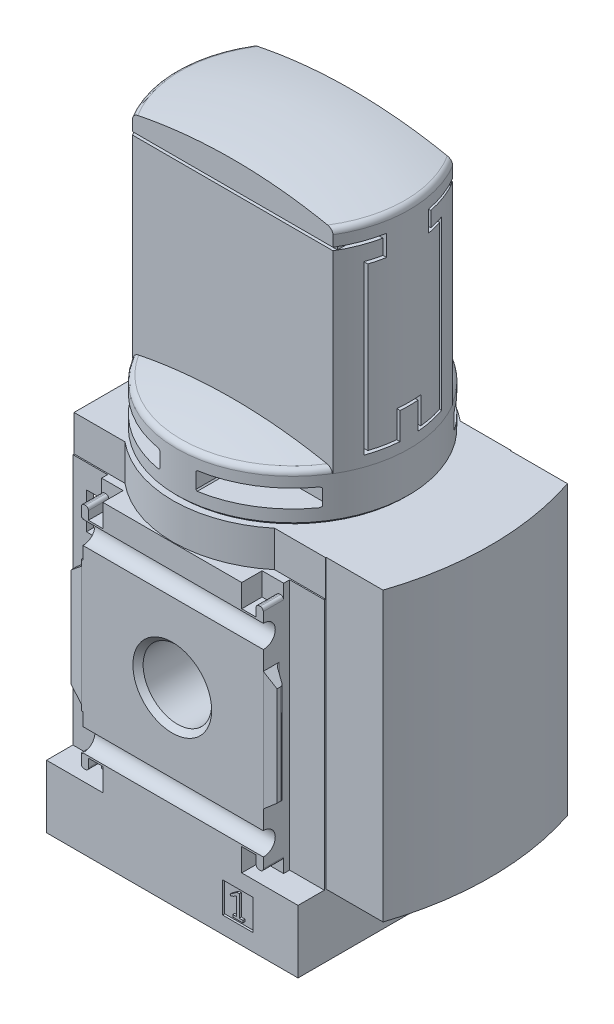
SolidWorks part; units mm, degrees
ref_plane "Front Plane" through (0, 0, 0) normal (0, 0, 1) x (1, 0, 0)
ref_plane "Top Plane" through (0, 0, 0) normal (0, 1, 0) x (1, 0, 0)
ref_plane "Right Plane" through (0, 0, 0) normal (1, 0, 0) x (0, 0, -1)
ref_plane "Plane1" through (0, 27, 0) normal (0, 1, 0) x (1, 0, 0)
sketch "Sketch1" plane through (0, 27, 0) normal (0, 1, 0) x (1, 0, 0)
  line L0 (-21, -15.5) -> (-12.5, -15.5)
  line L1 (12.5, -15.5) -> (21, -15.5)
  line L2 (21, -15.5) -> (21, 15.5)
  line L3 (21, 15.5) -> (12.5, 15.5)
  line L4 (-12.5, 15.5) -> (-21, 15.5)
  line L5 (-21, 15.5) -> (-21, -15.5)
  arc A0 (-12.5, -15.5) -> (12.5, -15.5) centre (0, -0.3889) ccw
  arc A1 (12.5, 15.5) -> (-12.5, 15.5) centre (0, 0.3889) ccw
extrude "Boss-Extrude1" add sketch "Sketch1" against normal blind 48
ref_plane "Plane2" through (0, 0, 0) normal (0, 0, 1) x (1, 0, 0)
sketch "Sketch2" plane through (0, 0, 0) normal (0, 0, 1) x (1, 0, 0)
  line L0 (-21, -21) -> (21, -21)
  line L1 (21, -21) -> (21, 21)
  line L2 (21, 21) -> (-21, 21)
  line L3 (-21, 21) -> (-21, -21)
extrude "Boss-Extrude2" add sketch "Sketch2" against normal blind 20.1 and the other way blind 20.1
ref_plane "Plane3" through (0, -31.5, 0) normal (0, 1, 0) x (1, 0, 0)
sketch "Sketch3" plane through (0, -31.5, 0) normal (0, 1, 0) x (1, 0, 0)
  line L0 (-21, -20.1) -> (21, -20.1)
  line L1 (21, -20.1) -> (21, 20.1)
  line L2 (21, 20.1) -> (-21, 20.1)
  line L3 (-21, 20.1) -> (-21, -20.1)
extrude "Boss-Extrude3" add sketch "Sketch3" along normal blind 10.5
ref_plane "Plane4" through (0, 27, 0) normal (0, 1, 0) x (1, 0, 0)
sketch "Sketch4" plane through (0, 27, 0) normal (0, 1, 0) x (1, 0, 0)
  line L0 (20.9, -15.4) -> (30.5, -15.4)
  line L1 (30.5, 15.4) -> (20.9, 15.4)
  line L2 (20.9, 15.4) -> (20.9, -15.4)
  arc A0 (30.5, -15.4) -> (30.5, 15.4) centre (-15.682, 0) ccw
extrude "Boss-Extrude4" add sketch "Sketch4" against normal blind 48
ref_plane "Plane5" through (0, 0, 0) normal (1, 0, 0) x (0, 0, -1)
sketch "Sketch5" plane through (0, 0, 0) normal (1, 0, 0) x (0, 0, -1)
  line L0 (-20.1, 0) -> (-20.1, 6.5785)
  line L1 (-20.1, 6.5785) -> (-19.244, 5.7225)
  line L2 (-19.244, 5.7225) -> (-7.799, 5.7225)
  line L3 (-7.799, 5.7225) -> (-6.943, 6.5785)
  line L4 (-6.943, 6.5785) -> (-6.943, 0)
  line L5 (-6.943, 0) -> (-20.1, 0)
  line L6 (-6.943, 0) -> (-20.1, 0) construction
revolve "Cut-Revolve1" cut sketch "Sketch5" angle 360 about L6 reverse direction yes
cosmetic thread "Cosmetic Thread1" parameters "D1"=13.157, "D2"=13.157
ref_plane "Plane6" through (0, 0, 0) normal (1, 0, 0) x (0, 0, -1)
sketch "Sketch6" plane through (0, 0, 0) normal (1, 0, 0) x (0, 0, -1)
  line L0 (6.943, 0) -> (6.943, 6.5785)
  line L1 (6.943, 6.5785) -> (7.799, 5.7225)
  line L2 (7.799, 5.7225) -> (19.244, 5.7225)
  line L3 (19.244, 5.7225) -> (20.1, 6.5785)
  line L4 (20.1, 6.5785) -> (20.1, 0)
  line L5 (20.1, 0) -> (6.943, 0)
  line L6 (20.1, 0) -> (6.943, 0) construction
revolve "Cut-Revolve2" cut sketch "Sketch6" angle 360 about L6 reverse direction yes
cosmetic thread "Cosmetic Thread2" parameters "D1"=13.157, "D2"=13.157
ref_plane "Plane7" through (0, 0, 20.1) normal (0, 0, 1) x (1, 0, 0)
sketch "Sketch7" plane through (0, 0, 20.1) normal (0, 0, 1) x (1, 0, 0)
  line L0 (8.4, -23.59) -> (8.4, -28.69)
  line L1 (8.4, -28.69) -> (13.5, -28.69)
  line L2 (13.5, -28.69) -> (13.5, -23.59)
  line L3 (13.5, -23.59) -> (8.4, -23.59)
  line L4 (9.6632, -25.02) -> (9.7613, -25.2755)
  line L5 (9.7613, -25.2755) -> (10.24, -25.0624)
  line L6 (10.24, -25.0624) -> (10.71, -24.78)
  line L7 (10.71, -24.78) -> (10.71, -27.76)
  line L8 (10.71, -27.76) -> (10.1, -27.76)
  line L9 (10.1, -27.76) -> (10.1, -28.14)
  line L10 (10.1, -28.14) -> (11.8, -28.14)
  line L11 (11.8, -28.14) -> (11.8, -27.76)
  line L12 (11.8, -27.76) -> (11.19, -27.76)
  line L13 (11.19, -27.76) -> (11.19, -24.21)
  line L14 (11.19, -24.21) -> (10.82, -24.21)
  line L15 (10.82, -24.21) -> (9.6632, -25.02)
extrude "Cut-Extrude1" cut sketch "Sketch7" against normal blind 0.35
ref_plane "Plane8" through (0, 0, -20.1) normal (0, 0, 1) x (1, 0, 0)
sketch "Sketch8" plane through (0, 0, -20.1) normal (0, 0, 1) x (1, 0, 0)
  line L0 (-13.5, -23.59) -> (-13.5, -28.69)
  line L1 (-13.5, -28.69) -> (-8.4, -28.69)
  line L2 (-8.4, -28.69) -> (-8.4, -23.59)
  line L3 (-8.4, -23.59) -> (-13.5, -23.59)
  line L4 (-12.0398, -25.2415) -> (-10.4706, -27.4826)
  line L5 (-10.5525, -27.64) -> (-12.15, -27.64)
  line L6 (-12.15, -27.64) -> (-12.15, -28.14)
  line L7 (-12.15, -28.14) -> (-9.75, -28.14)
  line L8 (-9.75, -28.14) -> (-9.75, -27.64)
  line L9 (-9.75, -27.64) -> (-11.5752, -25.0334)
  line L10 (-11.3704, -24.64) -> (-10.75, -24.64)
  line L11 (-10.25, -25.14) -> (-9.75, -25.14)
  line L12 (-10.75, -24.14) -> (-11.4664, -24.14)
  arc A0 (-11.4664, -24.14) -> (-12.0398, -25.2415) centre (-11.4664, -24.84) ccw
  arc A1 (-10.4706, -27.4826) -> (-10.5525, -27.64) centre (-10.5525, -27.54) cw
  arc A2 (-11.5752, -25.0334) -> (-11.3704, -24.64) centre (-11.3704, -24.89) cw
  arc A3 (-10.75, -24.64) -> (-10.25, -25.14) centre (-10.75, -25.14) cw
  arc A4 (-9.75, -25.14) -> (-10.75, -24.14) centre (-10.75, -25.14) ccw
extrude "Cut-Extrude2" cut sketch "Sketch8" along normal blind 0.35
ref_plane "Plane9" through (0, 0, 0) normal (1, 0, 0) x (0, 0, -1)
sketch "Sketch9" plane through (0, 0, 0) normal (1, 0, 0) x (0, 0, -1)
  line L0 (21.9, -15) -> (21.9, 15)
  line L1 (20.5, 13.167) -> (20.5, -13.167)
  arc A0 (20.5, -13.167) -> (21.9, -15) centre (20, -15) ccw
  arc A1 (21.9, 15) -> (20.5, 13.167) centre (20, 15) ccw
extrude "Cut-Extrude3" cut sketch "Sketch9" against normal blind 25 and the other way blind 25
ref_plane "Plane10" through (0, 0, 0) normal (1, 0, 0) x (0, 0, -1)
sketch "Sketch10" plane through (0, 0, 0) normal (1, 0, 0) x (0, 0, -1)
  line L0 (-21.9, 15) -> (-21.9, -15)
  line L1 (-20.5, -13.167) -> (-20.5, 13.167)
  arc A0 (-21.9, -15) -> (-20.5, -13.167) centre (-20, -15) ccw
  arc A1 (-20.5, 13.167) -> (-21.9, 15) centre (-20, 15) ccw
extrude "Cut-Extrude4" cut sketch "Sketch10" against normal blind 25 and the other way blind 25
ref_plane "Plane11" through (0, 0, 20.1) normal (0, 0, 1) x (1, 0, 0)
sketch "Sketch11" plane through (0, 0, 20.1) normal (0, 0, 1) x (1, 0, 0)
  line L0 (11.6, 21) -> (11.6, 17.2)
  line L1 (11.6, 17.2) -> (14, 17.2)
  line L2 (14, 17.2) -> (14, 18.6)
  line L3 (14.5, 19.1) -> (14.7, 19.1)
  line L4 (15.2, 18.6) -> (15.2, 9.95)
  line L5 (15.2, 9.95) -> (21.5, 4.6637)
  line L6 (21.5, 4.6637) -> (21.5, -4.6637)
  line L7 (21.5, -4.6637) -> (15.2, -9.95)
  line L8 (15.2, -9.95) -> (15.2, -18.6)
  line L9 (14.7, -19.1) -> (14.5, -19.1)
  line L10 (14, -18.6) -> (14, -17.2)
  line L11 (14, -17.2) -> (11.6, -17.2)
  line L12 (11.6, -17.2) -> (11.6, -21)
  line L13 (11.6, -21) -> (22, -21)
  line L14 (22, -21) -> (22, 21)
  line L15 (22, 21) -> (11.6, 21)
  arc A0 (14, 18.6) -> (14.5, 19.1) centre (14.5, 18.6) cw
  arc A1 (14.7, 19.1) -> (15.2, 18.6) centre (14.7, 18.6) cw
  arc A2 (15.2, -18.6) -> (14.7, -19.1) centre (14.7, -18.6) cw
  arc A3 (14.5, -19.1) -> (14, -18.6) centre (14.5, -18.6) cw
extrude "Cut-Extrude5" cut sketch "Sketch11" against normal blind 3.4 and the other way blind 3.4
ref_plane "Plane12" through (0, 0, 20.1) normal (0, 0, 1) x (1, 0, 0)
sketch "Sketch12" plane through (0, 0, 20.1) normal (0, 0, 1) x (1, 0, 0)
  line L0 (-22, -21) -> (-11.6, -21)
  line L1 (-11.6, -21) -> (-11.6, -17.2)
  line L2 (-11.6, -17.2) -> (-14, -17.2)
  line L3 (-14, -17.2) -> (-14, -18.6)
  line L4 (-14.5, -19.1) -> (-14.7, -19.1)
  line L5 (-15.2, -18.6) -> (-15.2, -9.95)
  line L6 (-15.2, -9.95) -> (-21.5, -4.6637)
  line L7 (-21.5, -4.6637) -> (-21.5, 4.6637)
  line L8 (-21.5, 4.6637) -> (-15.2, 9.95)
  line L9 (-15.2, 9.95) -> (-15.2, 18.6)
  line L10 (-14.7, 19.1) -> (-14.5, 19.1)
  line L11 (-14, 18.6) -> (-14, 17.2)
  line L12 (-14, 17.2) -> (-11.6, 17.2)
  line L13 (-11.6, 17.2) -> (-11.6, 21)
  line L14 (-11.6, 21) -> (-22, 21)
  line L15 (-22, 21) -> (-22, -21)
  arc A0 (-14, -18.6) -> (-14.5, -19.1) centre (-14.5, -18.6) cw
  arc A1 (-14.7, -19.1) -> (-15.2, -18.6) centre (-14.7, -18.6) cw
  arc A2 (-15.2, 18.6) -> (-14.7, 19.1) centre (-14.7, 18.6) cw
  arc A3 (-14.5, 19.1) -> (-14, 18.6) centre (-14.5, 18.6) cw
extrude "Cut-Extrude6" cut sketch "Sketch12" against normal blind 3.4 and the other way blind 3.4
ref_plane "Plane13" through (0, 0, -20.1) normal (0, 0, 1) x (1, 0, 0)
sketch "Sketch13" plane through (0, 0, -20.1) normal (0, 0, 1) x (1, 0, 0)
  line L0 (11.6, 21) -> (11.6, 17.2)
  line L1 (11.6, 17.2) -> (14, 17.2)
  line L2 (14, 17.2) -> (14, 18.6)
  line L3 (14.5, 19.1) -> (14.7, 19.1)
  line L4 (15.2, 18.6) -> (15.2, 9.95)
  line L5 (15.2, 9.95) -> (21.5, 4.6637)
  line L6 (21.5, 4.6637) -> (21.5, -4.6637)
  line L7 (21.5, -4.6637) -> (15.2, -9.95)
  line L8 (15.2, -9.95) -> (15.2, -18.6)
  line L9 (14.7, -19.1) -> (14.5, -19.1)
  line L10 (14, -18.6) -> (14, -17.2)
  line L11 (14, -17.2) -> (11.6, -17.2)
  line L12 (11.6, -17.2) -> (11.6, -21)
  line L13 (11.6, -21) -> (22, -21)
  line L14 (22, -21) -> (22, 21)
  line L15 (22, 21) -> (11.6, 21)
  arc A0 (14, 18.6) -> (14.5, 19.1) centre (14.5, 18.6) cw
  arc A1 (14.7, 19.1) -> (15.2, 18.6) centre (14.7, 18.6) cw
  arc A2 (15.2, -18.6) -> (14.7, -19.1) centre (14.7, -18.6) cw
  arc A3 (14.5, -19.1) -> (14, -18.6) centre (14.5, -18.6) cw
extrude "Cut-Extrude7" cut sketch "Sketch13" against normal blind 3.4 and the other way blind 3.4
ref_plane "Plane14" through (0, 0, -20.1) normal (0, 0, 1) x (1, 0, 0)
sketch "Sketch14" plane through (0, 0, -20.1) normal (0, 0, 1) x (1, 0, 0)
  line L0 (-22, -21) -> (-11.6, -21)
  line L1 (-11.6, -21) -> (-11.6, -17.2)
  line L2 (-11.6, -17.2) -> (-14, -17.2)
  line L3 (-14, -17.2) -> (-14, -18.6)
  line L4 (-14.5, -19.1) -> (-14.7, -19.1)
  line L5 (-15.2, -18.6) -> (-15.2, -9.95)
  line L6 (-15.2, -9.95) -> (-21.5, -4.6637)
  line L7 (-21.5, -4.6637) -> (-21.5, 4.6637)
  line L8 (-21.5, 4.6637) -> (-15.2, 9.95)
  line L9 (-15.2, 9.95) -> (-15.2, 18.6)
  line L10 (-14.7, 19.1) -> (-14.5, 19.1)
  line L11 (-14, 18.6) -> (-14, 17.2)
  line L12 (-14, 17.2) -> (-11.6, 17.2)
  line L13 (-11.6, 17.2) -> (-11.6, 21)
  line L14 (-11.6, 21) -> (-22, 21)
  line L15 (-22, 21) -> (-22, -21)
  arc A0 (-14, -18.6) -> (-14.5, -19.1) centre (-14.5, -18.6) cw
  arc A1 (-14.7, -19.1) -> (-15.2, -18.6) centre (-14.7, -18.6) cw
  arc A2 (-15.2, 18.6) -> (-14.7, 19.1) centre (-14.7, 18.6) cw
  arc A3 (-14.5, 19.1) -> (-14, 18.6) centre (-14.5, 18.6) cw
extrude "Cut-Extrude8" cut sketch "Sketch14" against normal blind 3.4 and the other way blind 3.4
ref_plane "Plane15" through (0, 0, 0) normal (0, 1, 0) x (1, 0, 0)
sketch "Sketch15" plane through (0, 0, 0) normal (0, 1, 0) x (1, 0, 0)
  line L0 (-22.2, 25.1) -> (-22.2, 15.7)
  line L1 (-22.2, 15.7) -> (-15.2, 15.7)
  line L2 (-15.2, 15.7) -> (-15.2, 17.4001)
  line L3 (-15.6493, 18.1191) -> (-16.9192, 18.7385)
  line L4 (-17.2, 19.1879) -> (-17.2, 19.8)
  line L5 (-17.2, 19.8) -> (-15.2, 20.1)
  line L6 (-15.2, 20.1) -> (15.2, 20.1)
  line L7 (15.2, 20.1) -> (17.2, 19.8)
  line L8 (17.2, 19.8) -> (17.2, 19.1879)
  line L9 (16.9192, 18.7385) -> (15.6493, 18.1191)
  line L10 (15.2, 17.4001) -> (15.2, 15.7)
  line L11 (15.2, 15.7) -> (22.2, 15.7)
  line L12 (22.2, 15.7) -> (22.2, 25.1)
  line L13 (22.2, 25.1) -> (-22.2, 25.1)
  arc A0 (-15.2, 17.4001) -> (-15.6493, 18.1191) centre (-16, 17.4001) ccw
  arc A1 (-16.9192, 18.7385) -> (-17.2, 19.1879) centre (-16.7, 19.1879) cw
  arc A2 (17.2, 19.1879) -> (16.9192, 18.7385) centre (16.7, 19.1879) cw
  arc A3 (15.6493, 18.1191) -> (15.2, 17.4001) centre (16, 17.4001) ccw
extrude "Cut-Extrude9" cut sketch "Sketch15" against normal blind 21 and the other way blind 21
ref_plane "Plane16" through (0, 0, 0) normal (0, 1, 0) x (1, 0, 0)
sketch "Sketch16" plane through (0, 0, 0) normal (0, 1, 0) x (1, 0, 0)
  line L0 (-22.2, -15.7) -> (-22.2, -25.1)
  line L1 (-22.2, -25.1) -> (22.2, -25.1)
  line L2 (22.2, -25.1) -> (22.2, -15.7)
  line L3 (22.2, -15.7) -> (15.2, -15.7)
  line L4 (15.2, -15.7) -> (15.2, -17.4001)
  line L5 (15.6493, -18.1191) -> (16.9192, -18.7385)
  line L6 (17.2, -19.1879) -> (17.2, -19.8)
  line L7 (17.2, -19.8) -> (15.2, -20.1)
  line L8 (15.2, -20.1) -> (-15.2, -20.1)
  line L9 (-15.2, -20.1) -> (-17.2, -19.8)
  line L10 (-17.2, -19.8) -> (-17.2, -19.1879)
  line L11 (-16.9192, -18.7385) -> (-15.6493, -18.1191)
  line L12 (-15.2, -17.4001) -> (-15.2, -15.7)
  line L13 (-15.2, -15.7) -> (-22.2, -15.7)
  arc A0 (15.2, -17.4001) -> (15.6493, -18.1191) centre (16, -17.4001) ccw
  arc A1 (16.9192, -18.7385) -> (17.2, -19.1879) centre (16.7, -19.1879) cw
  arc A2 (-17.2, -19.1879) -> (-16.9192, -18.7385) centre (-16.7, -19.1879) cw
  arc A3 (-15.6493, -18.1191) -> (-15.2, -17.4001) centre (-16, -17.4001) ccw
extrude "Cut-Extrude10" cut sketch "Sketch16" against normal blind 21 and the other way blind 21
ref_plane "Plane17" through (0, 0, 0) normal (0, 0, 1) x (1, 0, 0)
sketch "Sketch17" plane through (0, 0, 0) normal (0, 0, 1) x (1, 0, 0)
  line L0 (19.5, 68.8033) -> (19.5, 34.25)
  line L1 (19.5, 34.25) -> (18.5, 34.25)
  line L2 (18.5, 34.25) -> (18.5, 27)
  line L3 (18.5, 27) -> (0, 27)
  line L4 (0, 27) -> (0, 72)
  line L5 (0, 27) -> (0, 72) construction
  arc A0 (0, 72) -> (18.7342, 69.7755) centre (0, -8) cw
  arc A1 (18.7342, 69.7755) -> (19.5, 68.8033) centre (18.5, 68.8033) cw
revolve "Revolve1" add sketch "Sketch17" angle 360 about L5 reverse direction yes
ref_plane "Plane18" through (0, 0, 0) normal (1, 0, 0) x (0, 0, -1)
sketch "Sketch18" plane through (0, 0, 0) normal (1, 0, 0) x (0, 0, -1)
  line L0 (-30, 82) -> (-30, 27)
  line L1 (-30, 27) -> (-10, 27)
  line L2 (-10, 27) -> (-10, 66.5)
  line L3 (-10, 66.5) -> (-9.5, 66.5)
  line L4 (-9.5, 66.5) -> (-9.5, 67)
  line L5 (-9.5, 67) -> (-10, 67)
  line L6 (-10, 67) -> (-10, 72)
  line L7 (-10, 72) -> (10, 72)
  line L8 (10, 72) -> (10, 67)
  line L9 (10, 67) -> (9.5, 67)
  line L10 (9.5, 67) -> (9.5, 66.5)
  line L11 (9.5, 66.5) -> (10, 66.5)
  line L12 (10, 66.5) -> (10, 27)
  line L13 (10, 27) -> (30, 27)
  line L14 (30, 27) -> (30, 82)
  line L15 (30, 82) -> (-30, 82)
extrude "Cut-Extrude11" cut sketch "Sketch18" against normal blind 19.5 and the other way blind 19.5
ref_plane "Plane19" through (0, 0, 0) normal (0, 0, 1) x (1, 0, 0)
sketch "Sketch19" plane through (0, 0, 0) normal (0, 0, 1) x (1, 0, 0)
  line L0 (19.4, 34.2152) -> (19.4, 27.5)
  line L1 (19.4, 27.5) -> (18.9, 27)
  line L2 (18.9, 27) -> (0, 27)
  line L3 (0, 27) -> (0, 37.3879)
  line L4 (0, 27) -> (0, 37.3879) construction
  arc A0 (0, 37.3879) -> (18.6329, 35.1877) centre (0, -42.6121) cw
  arc A1 (18.6329, 35.1877) -> (19.4, 34.2152) centre (18.4, 34.2152) cw
revolve "Revolve2" add sketch "Sketch19" angle 360 about L4 reverse direction yes
ref_plane "Plane20" through (0, 0, 20.1) normal (0, 0, 1) x (1, 0, 0)
sketch "Sketch20" plane through (0, 0, 20.1) normal (0, 0, 1) x (1, 0, 0)
  line L0 (3, 32.3) -> (3, 29.7)
  line L1 (3, 29.7) -> (3.2, 29.5)
  line L2 (3.2, 29.5) -> (15.8, 29.5)
  line L3 (15.8, 29.5) -> (16, 29.7)
  line L4 (16, 29.7) -> (16, 32.3)
  line L5 (16, 32.3) -> (15.8, 32.5)
  line L6 (15.8, 32.5) -> (3.2, 32.5)
  line L7 (3.2, 32.5) -> (3, 32.3)
extrude "Cut-Extrude12" cut sketch "Sketch20" against normal blind 10
ref_plane "Plane21" through (0, 0, 20.1) normal (0, 0, 1) x (1, 0, 0)
sketch "Sketch21" plane through (0, 0, 20.1) normal (0, 0, 1) x (1, 0, 0)
  line L0 (-16, 32.3) -> (-16, 29.7)
  line L1 (-16, 29.7) -> (-15.8, 29.5)
  line L2 (-15.8, 29.5) -> (-3.2, 29.5)
  line L3 (-3.2, 29.5) -> (-3, 29.7)
  line L4 (-3, 29.7) -> (-3, 32.3)
  line L5 (-3, 32.3) -> (-3.2, 32.5)
  line L6 (-3.2, 32.5) -> (-15.8, 32.5)
  line L7 (-15.8, 32.5) -> (-16, 32.3)
extrude "Cut-Extrude13" cut sketch "Sketch21" against normal blind 10
ref_plane "Plane22" through (0, 0, -20.1) normal (0, 0, 1) x (1, 0, 0)
sketch "Sketch22" plane through (0, 0, -20.1) normal (0, 0, 1) x (1, 0, 0)
  line L0 (-16, 32.3) -> (-16, 29.7)
  line L1 (-16, 29.7) -> (-15.8, 29.5)
  line L2 (-15.8, 29.5) -> (-3.2, 29.5)
  line L3 (-3.2, 29.5) -> (-3, 29.7)
  line L4 (-3, 29.7) -> (-3, 32.3)
  line L5 (-3, 32.3) -> (-3.2, 32.5)
  line L6 (-3.2, 32.5) -> (-15.8, 32.5)
  line L7 (-15.8, 32.5) -> (-16, 32.3)
extrude "Cut-Extrude14" cut sketch "Sketch22" along normal blind 10
ref_plane "Plane23" through (0, 0, -20.1) normal (0, 0, 1) x (1, 0, 0)
sketch "Sketch23" plane through (0, 0, -20.1) normal (0, 0, 1) x (1, 0, 0)
  line L0 (3, 32.3) -> (3, 29.7)
  line L1 (3, 29.7) -> (3.2, 29.5)
  line L2 (3.2, 29.5) -> (15.8, 29.5)
  line L3 (15.8, 29.5) -> (16, 29.7)
  line L4 (16, 29.7) -> (16, 32.3)
  line L5 (16, 32.3) -> (15.8, 32.5)
  line L6 (15.8, 32.5) -> (3.2, 32.5)
  line L7 (3.2, 32.5) -> (3, 32.3)
extrude "Cut-Extrude15" cut sketch "Sketch23" along normal blind 10
ref_plane "Plane24" through (37.5, 0, 0) normal (1, 0, 0) x (0, 0, -1)
sketch "Sketch24" plane through (37.5, 0, 0) normal (1, 0, 0) x (0, 0, -1)
  line L0 (-10, 66.5) -> (-4, 66.5)
  line L1 (-4, 66.5) -> (-4, 64)
  line L2 (-4, 64) -> (-6.5, 64)
  line L3 (-6.5, 64) -> (-6.5, 36)
  line L4 (-6.5, 36) -> (-1.5, 36)
  line L5 (-1.5, 36) -> (-1.5, 40.5)
  line L6 (-1.5, 40.5) -> (1.5, 40.5)
  line L7 (1.5, 40.5) -> (1.5, 36)
  line L8 (1.5, 36) -> (6.5, 36)
  line L9 (6.5, 36) -> (6.5, 64)
  line L10 (6.5, 64) -> (4, 64)
  line L11 (4, 64) -> (4, 66.5)
  line L12 (4, 66.5) -> (10, 66.5)
  line L13 (10, 66.5) -> (10, 67)
  line L14 (10, 67) -> (3.5, 67)
  line L15 (3.5, 67) -> (3.5, 63.5)
  line L16 (3.5, 63.5) -> (6, 63.5)
  line L17 (6, 63.5) -> (6, 36.5)
  line L18 (6, 36.5) -> (2, 36.5)
  line L19 (2, 36.5) -> (2, 41)
  line L20 (2, 41) -> (-2, 41)
  line L21 (-2, 41) -> (-2, 36.5)
  line L22 (-2, 36.5) -> (-6, 36.5)
  line L23 (-6, 36.5) -> (-6, 63.5)
  line L24 (-6, 63.5) -> (-3.5, 63.5)
  line L25 (-3.5, 63.5) -> (-3.5, 67)
  line L26 (-3.5, 67) -> (-10, 67)
  line L27 (-10, 67) -> (-10, 66.5)
extrude "Cut-Extrude16" cut sketch "Sketch24" against normal blind 20.5
ref_plane "Plane25" through (-21, 0, 0) normal (1, 0, 0) x (0, 0, -1)
sketch "Sketch25" plane through (-21, 0, 0) normal (1, 0, 0) x (0, 0, -1)
  line L0 (-10, 66.5) -> (10, 66.5)
  line L1 (10, 66.5) -> (10, 67)
  line L2 (10, 67) -> (-10, 67)
  line L3 (-10, 67) -> (-10, 66.5)
extrude "Cut-Extrude17" cut sketch "Sketch25" along normal blind 4.5
ref_plane "Plane26" through (0, 0, 0) normal (0, 0, 1) x (1, 0, 0)
sketch "Sketch26" plane through (0, 0, 0) normal (0, 0, 1) x (1, 0, 0)
  line L0 (0, -18.343) -> (5.7225, -18.343)
  line L1 (5.7225, -18.343) -> (5.7225, -30.644)
  line L2 (5.7225, -30.644) -> (6.5785, -31.5)
  line L3 (6.5785, -31.5) -> (0, -31.5)
  line L4 (0, -31.5) -> (0, -18.343)
  line L5 (0, -31.5) -> (0, -18.343) construction
revolve "Cut-Revolve3" cut sketch "Sketch26" angle 360 about L5 reverse direction yes
cosmetic thread "Cosmetic Thread3" parameters "D1"=9.728, "D2"=13.157
ref_plane "Plane27" through (0, 0, 0) normal (0, 0, 1) x (1, 0, 0)
sketch "Sketch27" plane through (0, 0, 0) normal (0, 0, 1) x (1, 0, 0)
  line L0 (-18.73, 10.97) -> (-14.92, 10.97)
  line L1 (-14.92, 10.97) -> (-14.92, 17.04)
  line L2 (-14.92, 17.04) -> (-18.73, 17.04)
  line L3 (-18.73, 17.04) -> (-18.73, 10.97)
extrude "Cut-Extrude18" cut sketch "Sketch27" against normal blind 22 and the other way blind 22
ref_plane "Plane28" through (0, 0, 0) normal (0, 0, 1) x (1, 0, 0)
sketch "Sketch28" plane through (0, 0, 0) normal (0, 0, 1) x (1, 0, 0)
  line L0 (-18.73, -17.03) -> (-14.92, -17.03)
  line L1 (-14.92, -17.03) -> (-14.92, -10.96)
  line L2 (-14.92, -10.96) -> (-18.73, -10.96)
  line L3 (-18.73, -10.96) -> (-18.73, -17.03)
extrude "Cut-Extrude19" cut sketch "Sketch28" against normal blind 22 and the other way blind 22
ref_plane "Plane29" through (-21, 0, 0) normal (1, 0, 0) x (0, 0, -1)
sketch "Sketch29" plane through (-21, 0, 0) normal (1, 0, 0) x (0, 0, -1)
  line L0 (-14.5, -18.95) -> (14.5, -18.95)
  line L1 (14.5, -18.95) -> (14.5, 18.95)
  line L2 (14.5, 18.95) -> (-14.5, 18.95)
  line L3 (-14.5, 18.95) -> (-14.5, -18.95)
extrude "Cut-Extrude20" cut sketch "Sketch29" against normal blind 11 and the other way blind 11
ref_plane "Plane30" through (0, 0, 0) normal (0, 1, 0) x (1, 0, 0)
sketch "Sketch30" plane through (0, 0, 0) normal (0, 1, 0) x (1, 0, 0)
  line L0 (-11.4891, -14.5) -> (-10, -14.5)
  line L1 (-10, -14.5) -> (-10, 14.5)
  line L2 (-10, 14.5) -> (-11.4891, 14.5)
  arc A0 (-11.4891, 14.5) -> (-11.4891, -14.5) centre (0, 0) ccw
extrude "Boss-Extrude5" add sketch "Sketch30" against normal blind 19 and the other way blind 19
ref_plane "Plane31" through (-19.9, 0, 0) normal (1, 0, 0) x (0, 0, -1)
sketch "Sketch31" plane through (-19.9, 0, 0) normal (1, 0, 0) x (0, 0, -1)
  line L0 (8.8, -21.3) -> (14.6, -21.3)
  line L1 (14.6, -21.3) -> (14.6, -17.1)
  line L2 (14.6, -17.1) -> (13.1633, -17.1)
  line L3 (8.8, -17.5) -> (8.8, -21.3)
  arc A0 (13.1633, -17.1) -> (8.8, -17.5) centre (11, -17.5) ccw
extrude "Boss-Extrude6" add sketch "Sketch31" along normal blind 9
ref_plane "Plane32" through (-19.9, 0, 0) normal (1, 0, 0) x (0, 0, -1)
sketch "Sketch32" plane through (-19.9, 0, 0) normal (1, 0, 0) x (0, 0, -1)
  line L0 (-14.6, 17.1) -> (-13.1633, 17.1)
  line L1 (-8.8, 17.5) -> (-8.8, 21.3)
  line L2 (-8.8, 21.3) -> (-14.6, 21.3)
  line L3 (-14.6, 21.3) -> (-14.6, 17.1)
  arc A0 (-13.1633, 17.1) -> (-8.8, 17.5) centre (-11, 17.5) ccw
extrude "Boss-Extrude7" add sketch "Sketch32" along normal blind 9
ref_plane "Plane33" through (-18, 0, 0) normal (1, 0, 0) x (0, 0, -1)
sketch "Sketch33" plane through (-18, 0, 0) normal (1, 0, 0) x (0, 0, -1)
  circle A0 centre (8.6, 6) radius 3.05
extrude "Boss-Extrude8" add sketch "Sketch33" along normal blind 5
